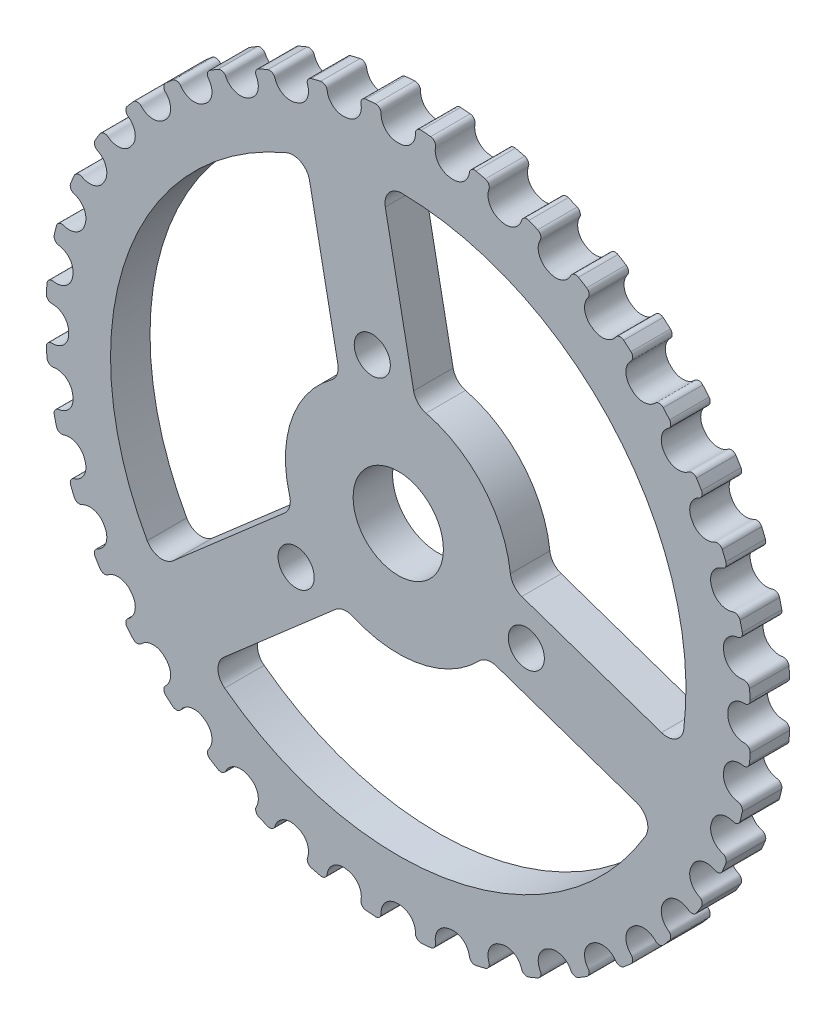
SolidWorks part; units mm, degrees
material "Thornel Mat VMA"
ref_plane "Front Plane" through (0, 0, 0) normal (0, 0, 1) x (1, 0, 0)
ref_plane "Top Plane" through (0, 0, 0) normal (0, 1, 0) x (1, 0, 0)
ref_plane "Right Plane" through (0, 0, 0) normal (1, 0, 0) x (0, 0, -1)
ref_axis "Axis1" through (0, 0, 55) along (0, 0, -1)
sketch "SketchRevolveGearBelt01" plane through (0, 0, 0) normal (1, 0, 0) x (0, 0, -1)
  line L0 (0, 0) -> (1, 0) construction
  line L1 (1.75, 0) -> (1.75, 31.2595)
  line L2 (1.75, 31.2595) -> (-1.75, 31.2595)
  line L3 (-1.75, 31.2595) -> (-1.75, 0)
  line L4 (-1.75, 0) -> (1.75, 0)
  dimension "GearBeltSide1" = 1.75
  dimension "GearBeltOutsideDiameter" = 31.2595
  dimension "GearBeltSide2" = 1.75
revolve "GearBelt01" add sketch "SketchRevolveGearBelt01" angle 360 about L0
sketch "SketchToothGearBelt01" plane through (0, 0, 0) normal (0, 0, 1) x (1, 0, 0)
  arc A0 (31.193, 2.0389) -> (31.193, -2.0389) centre (0, 0) cw
  spline S0 degree 3 poles (31.193, -2.0389) (31.1948, -2.0123) (31.1941, -1.9723) (31.1867, -1.9195) (31.178, -1.8806) (31.1661, -1.8425) (31.1511, -1.8054) (31.1331, -1.7698) (31.1123, -1.7357) (31.0888, -1.7034) (31.0627, -1.6731) (31.0343, -1.6451) (31.0036, -1.6195) (30.971, -1.5965) (30.9365, -1.5763) (30.9006, -1.5589) (30.8633, -1.5445) (30.825, -1.5332) (30.7859, -1.5251) (30.7463, -1.5201) (30.6992, -1.5186) (30.6277, -1.5196) (30.532, -1.516) (30.4198, -1.5026) (30.309, -1.4805) (30.2002, -1.4498) (30.0943, -1.4107) (29.9917, -1.3633) (29.8931, -1.3081) (29.7992, -1.2453) (29.7105, -1.1753) (29.6276, -1.0986) (29.5509, -1.0156) (29.481, -0.9268) (29.4182, -0.8329) (29.363, -0.7343) (29.3157, -0.6317) (29.2767, -0.5257) (29.246, -0.4169) (29.224, -0.3061) (29.2106, -0.1939) (29.2075, -0.1051) (29.2078, -0.0405) (29.2077, 0) (29.2078, 0.0405) (29.2075, 0.1051) (29.2106, 0.1939) (29.224, 0.3061) (29.246, 0.4169) (29.2767, 0.5257) (29.3157, 0.6317) (29.363, 0.7343) (29.4182, 0.8329) (29.481, 0.9268) (29.5509, 1.0156) (29.6276, 1.0986) (29.7105, 1.1753) (29.7992, 1.2453) (29.8931, 1.3081) (29.9917, 1.3633) (30.0943, 1.4107) (30.2002, 1.4498) (30.309, 1.4805) (30.4198, 1.5026) (30.532, 1.516) (30.6277, 1.5196) (30.6992, 1.5186) (30.7463, 1.5201) (30.7859, 1.5251) (30.825, 1.5332) (30.8633, 1.5445) (30.9006, 1.5589) (30.9365, 1.5763) (30.971, 1.5965) (31.0036, 1.6195) (31.0343, 1.6451) (31.0627, 1.6731) (31.0888, 1.7034) (31.1123, 1.7357) (31.1331, 1.7698) (31.1511, 1.8054) (31.1661, 1.8425) (31.178, 1.8806) (31.1867, 1.9195) (31.1941, 1.9723) (31.1948, 2.0123) (31.193, 2.0389) knots 0 0 0 0 0.012476 0.018713 0.024951 0.031189 0.037427 0.043665 0.049903 0.05614 0.062378 0.068616 0.074854 0.081092 0.08733 0.093567 0.099805 0.106043 0.112281 0.118519 0.124756 0.134376 0.152024 0.169672 0.18732 0.204968 0.222616 0.240264 0.257912 0.27556 0.293208 0.310856 0.328503 0.346151 0.363799 0.381447 0.399095 0.416743 0.434391 0.452039 0.469687 0.487335 0.493667 0.5 0.506333 0.512665 0.530313 0.547961 0.565609 0.583257 0.600905 0.618553 0.636201 0.653849 0.671497 0.689144 0.706792 0.72444 0.742088 0.759736 0.777384 0.795032 0.81268 0.830328 0.847976 0.865624 0.875244 0.881481 0.887719 0.893957 0.900195 0.906433 0.91267 0.918908 0.925146 0.931384 0.937622 0.94386 0.950097 0.956335 0.962573 0.968811 0.975049 0.981287 0.987524 1 1 1 1
extrude "ToothExtrudeCutGearBelt01" cut sketch "SketchToothGearBelt01" against normal blind 7.239 and the other way blind 7.239
pattern_circular "PatternGearBelt01" count 40 every 9 about axis through (0, 0, 55) along (0, 0, -1) of "ToothExtrudeCutGearBelt01"
sketch "BoreRevolveSketch" plane through (0, 0, 0) normal (1, 0, 0) x (0, 0, -1)
  line L0 (0, 0) -> (1, 0) construction
  line L1 (-7.239, 0) -> (7.239, 0)
  line L2 (7.239, 0) -> (7.239, 4)
  line L3 (7.239, 4) -> (-7.239, 4)
  line L4 (-7.239, 4) -> (-7.239, 0)
  dimension "BoreSide1" = 7.239
  dimension "TaperSide1" = 4
  dimension "BoreSide2" = 7.239
  dimension "TaperSide2" = 4
revolve "BoreRevolveCut" cut sketch "BoreRevolveSketch" angle 360 about L0
sketch "AuxiliarySketchGearBelt01" plane through (0, 0, 0) normal (0, 0, 1) x (1, 0, 0)
  circle A0 centre (0, 0) radius 31.831 construction
  dimension "PitchDiameter" = 63.6619
sketch "Sketch1" plane through (0, 0, -1.75) normal (0, 0, -1) x (-1, 0, 0)
  line L0 (-10.9417, -0.1387) -> (-23.3286, -4.3894) construction
  line L1 (-1.3627, 10.8574) -> (1.1496, 23.7101) construction
  line L2 (-10.9417, -0.1387) -> (-23.3286, -4.3894)
  line L3 (-1.3627, 10.8574) -> (1.1496, 23.7101)
  arc A0 (-25.3039, -3.1563) -> (-23.3286, -4.3894) centre (-23.8154, -2.9706) ccw construction
  arc A1 (-10.9417, -0.1387) -> (-9.9379, 1.1131) centre (-11.4285, 1.28) ccw construction
  arc A2 (-2.4651, 9.6914) -> (-1.3627, 10.8574) centre (-2.8348, 11.1451) ccw construction
  arc A3 (-2.4651, 9.6914) -> (-9.9379, 1.1131) centre (0, 0) ccw construction
  circle A4 centre (2.302, 11.7771) radius 1.6 construction
  arc A5 (1.1496, 23.7101) -> (-0.3427, 25.4977) centre (-0.3225, 23.9978) ccw construction
  arc A6 (-0.3427, 25.4977) -> (-25.3039, -3.1563) centre (0, 0) ccw construction
  arc A7 (-25.3039, -3.1563) -> (-23.3286, -4.3894) centre (-23.8154, -2.9706) ccw
  arc A8 (-10.9417, -0.1387) -> (-9.9379, 1.1131) centre (-11.4285, 1.28) ccw
  arc A9 (-2.4651, 9.6914) -> (-1.3627, 10.8574) centre (-2.8348, 11.1451) ccw
  arc A10 (-2.4651, 9.6914) -> (-9.9379, 1.1131) centre (0, 0) ccw
  circle A11 centre (2.302, 11.7771) radius 1.6
  arc A12 (1.1496, 23.7101) -> (-0.3427, 25.4977) centre (-0.3225, 23.9978) ccw
  arc A13 (-0.3427, 25.4977) -> (-25.3039, -3.1563) centre (0, 0) ccw
extrude "Cut-Extrude1" cut sketch "Sketch1" against normal blind 10
pattern_circular "CirPattern1" count 3 every 120 about axis through (0, 0, 0) along (0, 0, 1) of "Cut-Extrude1"
